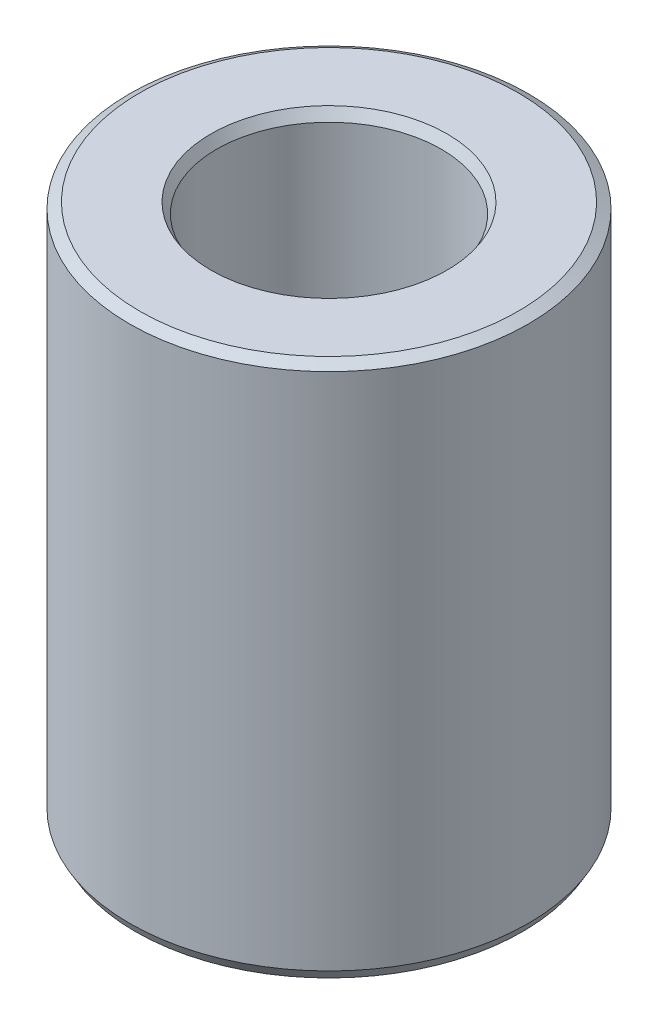
SolidWorks part; units mm, degrees
ref_plane "Front Plane" through (0, 0, 0) normal (0, 0, 1) x (1, 0, 0)
ref_plane "Top Plane" through (0, 0, 0) normal (0, 1, 0) x (1, 0, 0)
ref_plane "Right Plane" through (0, 0, 0) normal (1, 0, 0) x (0, 0, -1)
sketch "Sketch1" plane through (0, 0, 0) normal (0, 1, 0) x (1, 0, 0)
  circle A0 centre (0, 0) radius 55
  dimension "SLEEVE_OD" = 110
extrude "Boss-Extrude1" add sketch "Sketch1" along normal blind 147.5927
sketch "Sketch2" plane through (0, 0, 0) normal (0, 1, 0) x (1, 0, 0)
  circle A0 centre (0, 0) radius 30.9452
  dimension "BORE_D" = 61.8904
extrude "Cut-Extrude1" cut sketch "Sketch2" along normal through all
chamfer "Chamfer1" distance 1.6272 angle 60 4 edges at (0, 147.5927, 30.9452) (0, 0, 30.9452) (0, 0, 55) (0, 147.5927, 55) first distance on face at (0, 147.5927, 30.9452) first distance on face at (0, 0, 30.9452) first distance on face at (0, 147.5927, 55)
